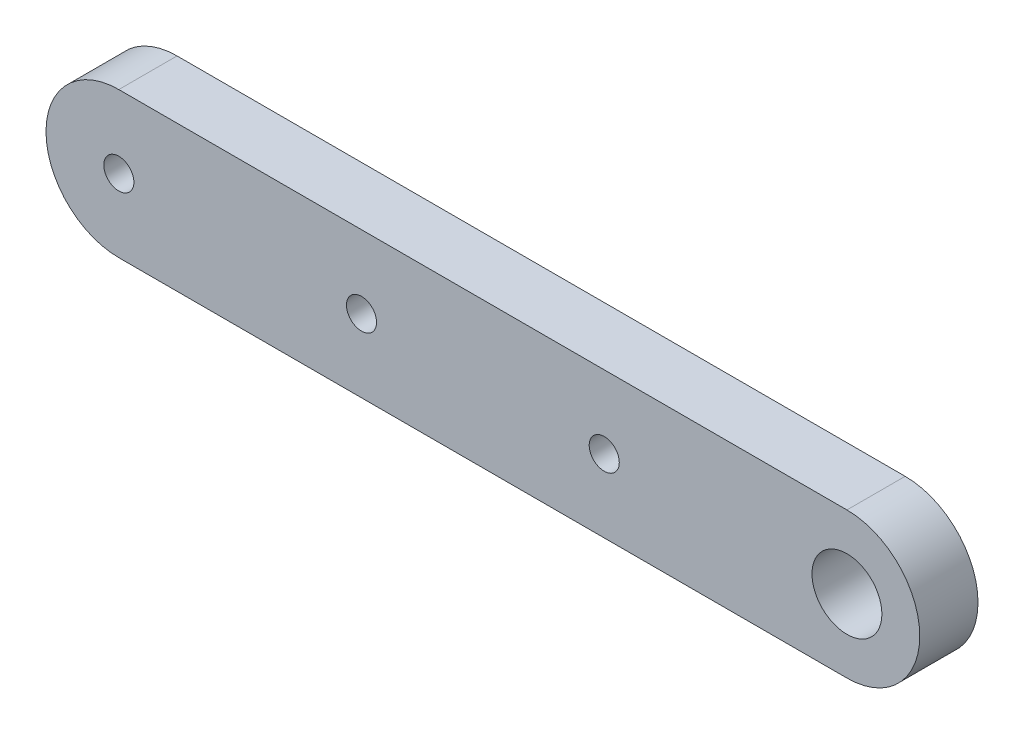
SolidWorks part; units mm, degrees
material "Pine"
ref_plane "Front Plane" through (0, 0, 0) normal (0, 0, 1) x (1, 0, 0)
ref_plane "Top Plane" through (0, 0, 0) normal (0, 1, 0) x (1, 0, 0)
ref_plane "Right Plane" through (0, 0, 0) normal (1, 0, 0) x (0, 0, -1)
sketch "Sketch1" plane through (0, 0, 0) normal (0, 0, 1) x (1, 0, 0)
  line L0 (0, 7.5) -> (75, 7.5)
  line L1 (75, -7.5) -> (0, -7.5)
  circle A0 centre (0, 0) radius 7.5
  circle A1 centre (75, 0) radius 7.5
  dimension "D1" = 75
  dimension "D2" = 15
extrude "Boss-Extrude1" add sketch "Sketch1" along normal blind 6 contours A1 L0 A0 L1 | A1 | A0 region at (37.5, 0, 0) region at (0, 0, 0) region at (75, 0, 0)
ref_plane "Plane1" through (0, 0, 3) normal (0, 0, 1) x (1, 0, 0)
sketch "Sketch2" plane through (0, 0, 6) normal (0, 0, 1) x (1, 0, 0)
  circle A0 centre (0, 0) radius 1.55
  circle A1 centre (75, 0) radius 1.55
  dimension "D1" = 3.1
extrude "Cut-Extrude1" cut sketch "Sketch2" against normal through all
pattern_linear "LPattern1" count 4 spacing 25 along (1, 0, 0) of "Cut-Extrude1"
sketch "Sketch3" plane through (0, 0, 6) normal (0, 0, 1) x (1, 0, 0)
  circle A0 centre (75, 0) radius 3.6
  dimension "D1" = 7.2
extrude "Cut-Extrude2" cut sketch "Sketch3" against normal through all
